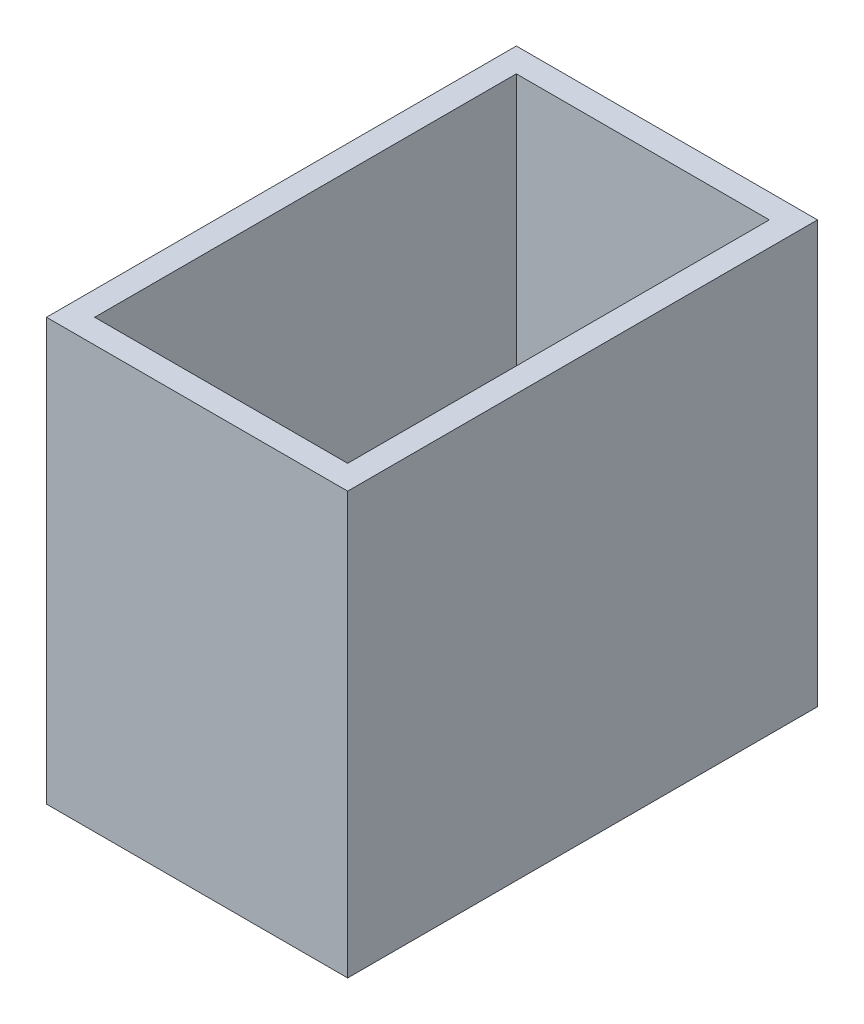
SolidWorks part; units mm, degrees
ref_plane "Front" through (0, 0, 0) normal (0, 0, 1) x (1, 0, 0)
ref_plane "Top" through (0, 0, 0) normal (0, 1, 0) x (1, 0, 0)
ref_plane "Right" through (0, 0, 0) normal (1, 0, 0) x (0, 0, -1)
sketch "Sketch1" plane through (0, 0, 0) normal (0, 1, 0) x (1, 0, 0)
  line L0 (-12.5, -19.5) -> (-12.5, 19.5)
  line L1 (-10.5, -17.5) -> (10.5, -17.5)
  line L2 (-10.5, -17.5) -> (-10.5, 17.5)
  line L3 (-10.5, 17.5) -> (10.5, 17.5)
  line L4 (10.5, -17.5) -> (10.5, 17.5)
  line L5 (-10.5, -17.5) -> (10.5, 17.5) construction
  line L6 (-10.5, 17.5) -> (10.5, -17.5) construction
  line L7 (-12.5, 19.5) -> (12.5, 19.5)
  line L8 (12.5, -19.5) -> (12.5, 19.5)
  line L9 (-12.5, -19.5) -> (12.5, -19.5)
  point P0 (0, 0)
  dimension "D1" = 35
  dimension "D2" = 21
  dimension "D3" = 2
extrude "Boss-Extrude1" add sketch "Sketch1" along normal blind 30
extrude "Boss-Extrude2" add sketch "Sketch1<2>" against normal blind 5 contours L1 L4 L3 L2 | L0 L9 L8 L7 L4 L1 L2 L3 region at (-12.0368, 0, 0) region at (0, 0, 0)
sketch "Sketch1<2>" plane through (0, 0, 0) normal (0, 1, 0) x (1, 0, 0) same geometry as "Sketch1"
sketch "Sketch4" plane through (0, 0, 0) normal (0, 1, 0) x (1, 0, 0)
  circle A0 centre (0, 0) radius 2.75
  point P2 (0, 0)
  point P4 (0, 0)
  dimension "D1" = 5.5
extrude "Cut-Extrude1" cut sketch "Sketch4" against normal through all both and the other way through all
